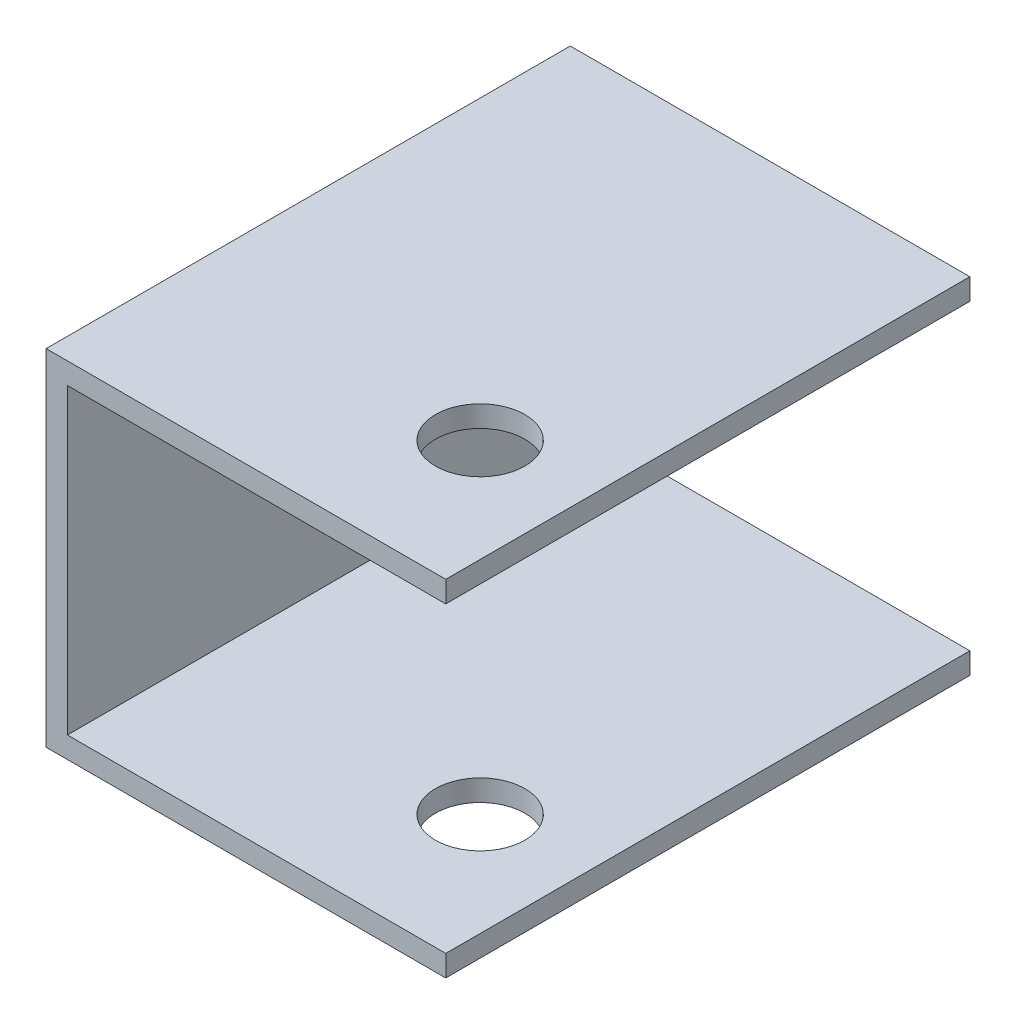
SolidWorks part; units mm, degrees
material "AISI 1020 Acero laminado en frío"
ref_plane "Alzado" through (0, 0, 0) normal (0, 0, 1) x (1, 0, 0)
ref_plane "Planta" through (0, 0, 0) normal (0, 1, 0) x (1, 0, 0)
ref_plane "Vista lateral" through (0, 0, 0) normal (1, 0, 0) x (0, 0, -1)
sketch "Croquis6" plane through (0, 0, 0) normal (0, 0, 1) x (1, 0, 0)
  line L0 (55, 22) -> (0, 22)
  line L1 (0, 22) -> (0, -22)
  line L2 (0, -22) -> (55, -22)
  line L3 (55, -22) -> (55, -25.1)
  line L4 (55, -25.1) -> (-3.1, -25.1)
  line L5 (-3.1, -25.1) -> (-3.1, 25.1)
  line L6 (-3.1, 25.1) -> (55, 25.1)
  line L7 (55, 25.1) -> (55, 22)
  point P3 (0, 0)
  dimension "D1" = 3.1
  dimension "D2" = 3.1
  dimension "D3" = 3.1
  dimension "D4" = 44
  dimension "D5" = 55
extrude "Saliente-Extruir3" add sketch "Croquis6" along normal mid plane 76.2
sketch "Croquis7" plane through (-3.1, 0, 0) normal (-1, 0, 0) x (0, 0, 1)
  circle A0 centre (0, 0) radius 6.5
  dimension "D1" = 13
extrude "Cortar-Extruir1" cut sketch "Croquis7" against normal blind 5 contours A0
sketch "Croquis8" plane through (0, -25.1, 0) normal (0, -1, 0) x (1, 0, 0)
  line L0 (0, 0) -> (31.2543, 0) construction
  line L1 (-3.1, 38.1) -> (55, 38.1) construction
  line L2 (55, 38.1) -> (55, -38.1) construction
  circle A0 centre (40, 18.1) radius 6.5
  dimension "D1" = 13
  dimension "D2" = 15
  dimension "D3" = 20
extrude "Cortar-Extruir2" cut sketch "Croquis8" against normal blind 70 contours A0
